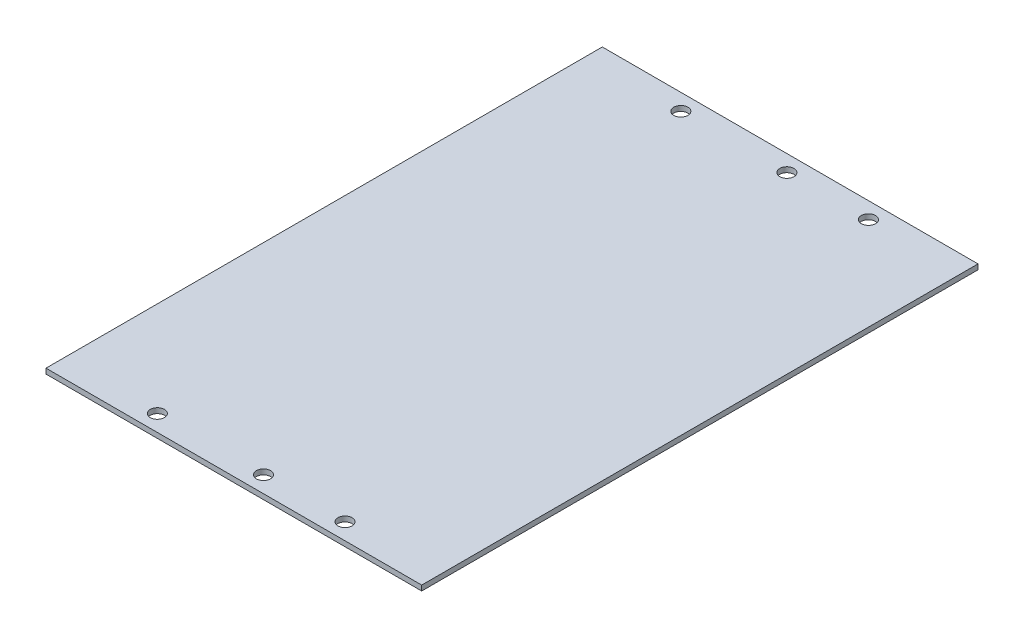
SolidWorks part; units mm, degrees
material "Zoltek Panex 33"
ref_plane "Front Plane" through (0, 0, 0) normal (0, 0, 1) x (1, 0, 0)
ref_plane "Top Plane" through (0, 0, 0) normal (0, 1, 0) x (1, 0, 0)
ref_plane "Right Plane" through (0, 0, 0) normal (1, 0, 0) x (0, 0, -1)
sketch "Sketch1" plane through (0, 0, 0) normal (0, 1, 0) x (1, 0, 0)
  line L0 (138.9, 215) -> (138.9, 202.3) construction
  line L5 (18.4, 202.3) -> (18.4, 215) construction
  line L6 (136.9, 0.005) -> (20.4, 0.005) construction
  line L7 (83.4, 163.1015) -> (83.4, 51.9035) construction
  line L8 (43.9375, 107.5025) -> (122.8625, 107.5025) construction
  line L9 (5.7, 0.005) -> (150.9, 0.005)
  line L10 (5.7, 0.005) -> (5.7, 215)
  line L11 (5.7, 215) -> (150.9, 215)
  line L12 (150.9, 0.005) -> (150.9, 215)
  line L13 (136.9, 215) -> (20.4, 215) construction
  line L14 (150.9, -30.995) -> (150.9, 246) construction
  line L15 (18.4, 0.005) -> (18.4, 12.705) construction
  circle A0 centre (42.4, 208.65) radius 2.75
  circle A1 centre (83.4, 208.65) radius 2.75
  circle A2 centre (114.9, 208.65) radius 2.75
  circle A3 centre (114.9, 6.355) radius 2.75
  circle A4 centre (83.4, 6.355) radius 2.75
  circle A5 centre (42.4, 6.355) radius 2.75
  circle A6 centre (42.4, 6.355) radius 4.75 construction
  dimension "D4" = 5.5
  dimension "D5" = 24
  dimension "D6" = 24
  dimension "D7" = 0
  dimension "D2" = 6.35
  dimension "D1" = 12.7
extrude "Boss-Extrude1" add sketch "Sketch1" along normal blind 2
